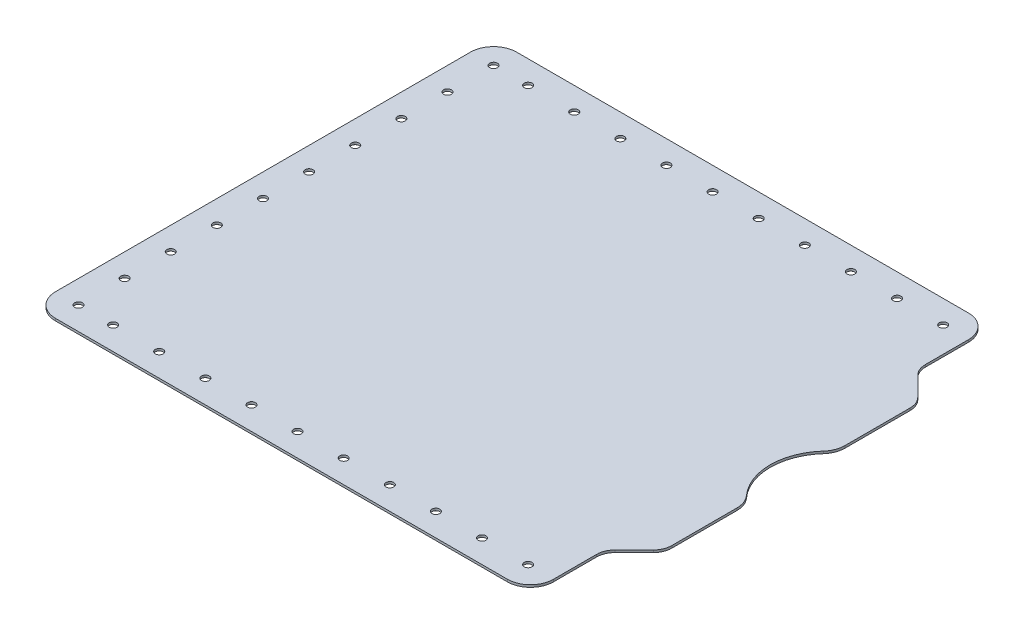
SolidWorks part; units mm, degrees
material "AISI 1020 Steel, Cold Rolled"
ref_plane "Front Plane" through (0, 0, 0) normal (0, 0, 1) x (1, 0, 0)
ref_plane "Top Plane" through (0, 0, 0) normal (0, 1, 0) x (1, 0, 0)
ref_plane "Right Plane" through (0, 0, 0) normal (1, 0, 0) x (0, 0, -1)
sketch "Sketch1" plane through (0, 0, 0) normal (0, 1, 0) x (1, 0, 0)
  line L1 (-114.5, 100) -> (114.5, 100)
  line L2 (-114.5, 100) -> (-114.5, -100)
  line L3 (-114.5, -100) -> (114.5, -100)
  line L4 (114.5, 100) -> (114.5, -100)
  line L5 (-114.5, 100) -> (114.5, -100) construction
  line L6 (-114.5, -100) -> (114.5, 100) construction
  point P0 (0, 0)
  dimension "D1" = 229
  dimension "D2" = 200
extrude "Boss-Extrude1" add sketch "Sketch1" along normal blind 1
sketch "Sketch2" plane through (0, 1, 0) normal (0, 1, 0) x (1, 0, 0)
  line L0 (114.5, 55) -> (101.5, 68)
  line L1 (114.5, -100) -> (114.5, 100) construction
  line L2 (101.5, 68) -> (101.5, 100)
  line L3 (114.5, 100) -> (-114.5, 100) construction
  line L4 (101.5, 100) -> (114.5, 100)
  line L5 (114.5, 100) -> (114.5, 55)
  line L6 (-55, 0) -> (55, 0) construction
  line L7 (101.5, -100) -> (114.5, -100)
  line L8 (101.5, -68) -> (101.5, -100)
  line L9 (114.5, -55) -> (101.5, -68)
  line L10 (114.5, -100) -> (114.5, -55)
  dimension "D1" = 45
  dimension "D2" = 32
  dimension "D3" = 13
extrude "Cut-Extrude1" cut sketch "Sketch2" against normal through all
fillet "Fillet1" radius 8 4 edges at (101.5, 0.5, 68) (114.5, 0.5, 55) (114.5, 0.5, -55) (101.5, 0.5, -68)
fillet "Fillet2" radius 10 4 edges at (-114.5, 0.5, -100) (-114.5, 0.5, 100) (101.5, 0.5, 100) (101.5, 0.5, -100)
hole_wizard "M3 Clearance Hole1" positions "Sketch3" profile "Sketch4" hole size "M3" standard "ANSI Metric" end condition through all
sketch "Sketch3" plane through (0, 0, 0) normal (0, -1, 0) x (-1, 0, 0)
  line L0 (-91.5, 100) -> (104.5, 100) construction
  line L1 (114.5, 90) -> (114.5, -90) construction
  point P0 (104.5, 90)
  point P13 (104.5, 70)
  point P14 (104.5, 50)
  point P15 (104.5, 30)
  point P16 (104.5, 10)
  point P17 (104.5, -10)
  point P18 (104.5, -30)
  point P19 (104.5, -50)
  point P20 (104.5, -70)
  point P21 (104.5, -90)
  dimension "D1" = 10
  dimension "D2" = 10
  dimension "D4" = 20
  dimension "D3" = 10
sketch "Sketch4" plane through (-104.5, 0, -90) normal (1, 0, 0) x (0, 0, -1)
  line L0 (0, 0) -> (0, 1)
  line L1 (0, 1) -> (1.7, 1)
  line L2 (1.7, 1) -> (1.7, 0.025)
  line L3 (1.7, 0.025) -> (1.725, 0)
  line L5 (1.725, 0) -> (0, 0)
  line L6 (-1.7, 0.025) -> (-1.725, 0) construction
  line L11 (0, -6.35) -> (0, 107.95) construction
  dimension "Thru Hole Dia." = 3.4
  dimension "Thru Hole Depth" = 1
  dimension "Near C'Sink Dia." = 3.45
  dimension "Near C'Sink Angle" = 90
hole_wizard "M3 Clearance Hole2" positions "Sketch5" profile "Sketch6" hole size "M3" standard "ANSI Metric" end condition through all
sketch "Sketch5" plane through (0, 0, 0) normal (0, -1, 0) x (-1, 0, 0)
  line L0 (-101.5, 90) -> (-101.5, 71.3137) construction
  line L1 (-91.5, 100) -> (104.5, 100) construction
  line L2 (-0.55, 0) -> (0.55, 0) construction
  point P0 (-90.5, 90)
  point P14 (-70.5, 90)
  point P15 (-50.5, 90)
  point P16 (-30.5, 90)
  point P17 (-10.5, 90)
  point P18 (9.5, 90)
  point P19 (29.5, 90)
  point P20 (49.5, 90)
  point P21 (69.5, 90)
  point P22 (89.5, 90)
  point P25 (89.5, -90)
  point P26 (69.5, -90)
  point P27 (49.5, -90)
  point P28 (29.5, -90)
  point P29 (9.5, -90)
  point P30 (-10.5, -90)
  point P31 (-30.5, -90)
  point P32 (-50.5, -90)
  point P33 (-70.5, -90)
  point P34 (-90.5, -90)
  dimension "D1" = 11
  dimension "D2" = 10
  dimension "D4" = 20
  dimension "D3" = 10
sketch "Sketch6" plane through (90.5, 0, -90) normal (1, 0, 0) x (0, 0, -1)
  line L0 (0, 0) -> (0, 1)
  line L1 (0, 1) -> (1.7, 1)
  line L2 (1.7, 1) -> (1.7, 0.025)
  line L3 (1.7, 0.025) -> (1.725, 0)
  line L5 (1.725, 0) -> (0, 0)
  line L6 (-1.7, 0.025) -> (-1.725, 0) construction
  line L11 (0, -6.35) -> (0, 107.95) construction
  dimension "Thru Hole Dia." = 3.4
  dimension "Thru Hole Depth" = 1
  dimension "Near C'Sink Dia." = 3.45
  dimension "Near C'Sink Angle" = 90
sketch "Sketch7" plane through (0, 0, 0) normal (0, -1, 0) x (-1, 0, 0)
  line L0 (-114.5, 0) -> (-130.5, 0) construction
  line L1 (-114.5, -51.6863) -> (-114.5, 51.6863) construction
  circle A0 centre (-130.5, 0) radius 25
  dimension "D2" = 50
  dimension "D1" = 16
extrude "Cut-Extrude2" cut sketch "Sketch7" against normal blind 10
fillet "Fillet3" radius 10 2 edges at (114.5, 0.5, 19.2094) (114.5, 0.5, -19.2094)
